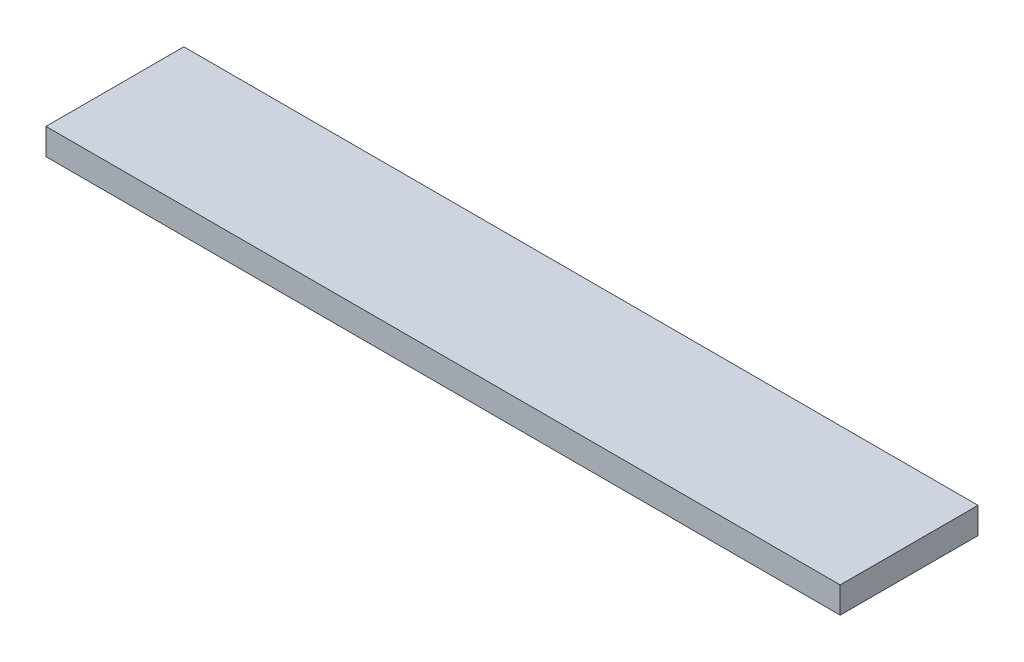
SolidWorks part; units mm, degrees
ref_plane "Front Plane" through (0, 0, 0) normal (0, 0, 1) x (1, 0, 0)
ref_plane "Top Plane" through (0, 0, 0) normal (0, 1, 0) x (1, 0, 0)
ref_plane "Right Plane" through (0, 0, 0) normal (1, 0, 0) x (0, 0, -1)
sketch "Sketch1" plane through (0, 0, 0) normal (0, 1, 0) x (1, 0, 0)
  line L1 (-60.5, -10.5) -> (60.5, -10.5)
  line L2 (-60.5, -10.5) -> (-60.5, 10.5)
  line L3 (-60.5, 10.5) -> (60.5, 10.5)
  line L4 (60.5, -10.5) -> (60.5, 10.5)
  line L5 (-60.5, -10.5) -> (60.5, 10.5) construction
  line L6 (-60.5, 10.5) -> (60.5, -10.5) construction
  point P0 (0, 0)
  dimension "D1" = 121
  dimension "D2" = 21
extrude "Boss-Extrude1" add sketch "Sketch1" along normal blind 4
